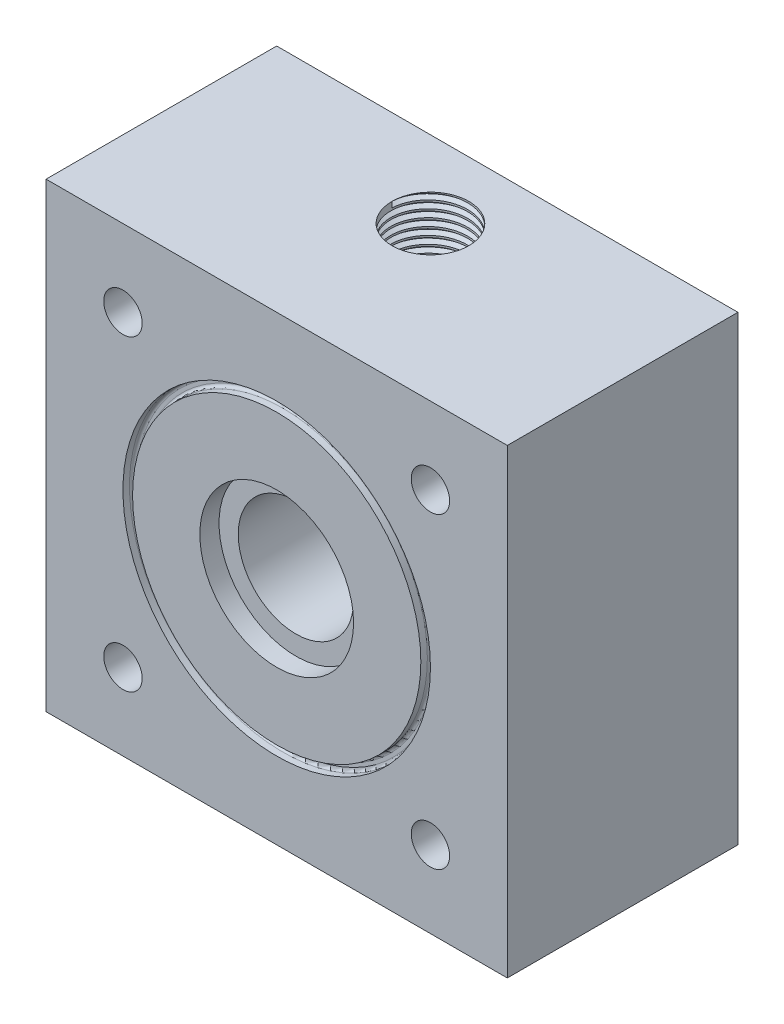
SolidWorks part; units mm, degrees
ref_plane "Front Plane" through (0, 0, 0) normal (0, 0, 1) x (1, 0, 0)
ref_plane "Top Plane" through (0, 0, 0) normal (0, 1, 0) x (1, 0, 0)
ref_plane "Right Plane" through (0, 0, 0) normal (1, 0, 0) x (0, 0, -1)
sketch "Sketch2" plane through (0, 0, 0) normal (0, 0, 1) x (1, 0, 0)
  line L1 (-38.1, -38.1) -> (38.1, -38.1)
  line L2 (-38.1, -38.1) -> (-38.1, 38.1)
  line L3 (-38.1, 38.1) -> (38.1, 38.1)
  line L4 (38.1, -38.1) -> (38.1, 38.1)
  line L5 (-38.1, -38.1) -> (38.1, 38.1) construction
  line L6 (-38.1, 38.1) -> (38.1, -38.1) construction
  point P0 (0, 0)
  dimension "D1" = 76.2
  dimension "D2" = 76.2
extrude "Boss-Extrude1" add sketch "Sketch2" along normal blind 38.1
sketch "Sketch3" plane through (0, 0, 0) normal (0, 0, -1) x (-1, 0, 0)
  circle A0 centre (0, 0) radius 25.4
  circle A1 centre (0, 0) radius 19.05
  dimension "D1" = 50.8
  dimension "D2" = 38.1
extrude "Cut-Extrude1" cut sketch "Sketch3" against normal blind 3.81
sketch "Sketch5" plane through (0, 38.1, 0) normal (0, 1, 0) x (1, 0, 0)
  line L0 (38.1, 0) -> (-38.1, 0) construction
  circle A0 centre (0, -12.7) radius 6.35
  point P4 (0, 0)
  dimension "D1" = 12.7
  dimension "D2" = 12.7
extrude "Cut-Extrude3" cut sketch "Sketch5" against normal blind 38.1
thread "Thread1" pitch 1.27 method cut profile "Thread Profile2" start angle 0, offset 0, length 12.7, pitch 1.27, diameter 12.7
ref_plane "Plane2" through (-6.35, 38.1, 12.7) normal (0, 0, 1) x (-1, 0, 0)
sketch "Thread Profile2" plane through (-6.35, 38.1, 12.7) normal (0, 0, 1) x (-1, 0, 0)
  line L0 (0, 0) -> (0, 1.27) construction
  line L1 (0, 0) -> (0.6874, 0.3969)
  line L2 (0.6874, 0.3969) -> (0.6874, 0.5556)
  line L3 (0.6874, 0.5556) -> (0, 0.9525)
  line L4 (0.6874, 0.4762) -> (0, 0.4762) construction
  line L11 (0, 0) -> (0, 0.9525)
  point P2 (0, 0)
  dimension "Pitch" = 1.27
  dimension "Profile_Angle" = 60
  dimension "Profile_Land" = 0.1588
  dimension "Profile_Height" = 0.6874
sketch "Sketch17" plane through (0, 0, 38.1) normal (0, 0, 1) x (1, 0, 0)
  line L0 (-38.1, 38.1) -> (-38.1, -38.1) construction
  line L1 (38.1, 38.1) -> (-38.1, 38.1) construction
  circle A0 centre (-25.4, 25.4) radius 3.175
  circle A1 centre (25.4, 25.4) radius 3.175
  circle A2 centre (25.4, -25.4) radius 3.175
  circle A3 centre (-25.4, -25.4) radius 3.175
  point P15 (0, 0)
  dimension "D1" = 6.35
  dimension "D2" = 12.7
  dimension "D3" = 12.7
  dimension "D4" = 4
extrude "Cut-Extrude5" cut sketch "Sketch17" against normal through all
sketch "Sketch18" plane through (0, 0, 38.1) normal (0, 0, 1) x (1, 0, 0)
  circle A0 centre (0, 0) radius 12.7
  dimension "D1" = 25.4
extrude "Cut-Extrude6" cut sketch "Sketch18" against normal blind 3.175
sketch "Sketch21" plane through (0, 0, 0) normal (0, 0, -1) x (-1, 0, 0)
  circle A0 centre (0, 0) radius 9.525
  dimension "D1" = 19.05
extrude "Cut-Extrude9" cut sketch "Sketch21" against normal through all
chamfer "Chamfer1" distance 2.54 angle 45 1 edges at (-9.525, 0, 0)
chamfer "Chamfer2" distance 0.508 angle 45 1 edges at (-25.4, 0, 0)
sketch "Sketch22" plane through (0, 0, 38.1) normal (0, 0, 1) x (1, 0, 0)
  circle A0 centre (0, 0) radius 23.8125
  circle A1 centre (0, 0) radius 25.4
  dimension "D1" = 47.625
  dimension "D2" = 50.8
extrude "Cut-Extrude11" cut sketch "Sketch22" against normal blind 1.5875
fillet "Fillet2" radius 0.508 2 edges at (25.4, 0, 36.5125) (23.8125, 0, 36.5125)
chamfer "Chamfer3" distance 0.508 angle 45 1 edges at (-19.05, 0, 0)
fillet "Fillet3" radius 0.762 1 edges at (-25.4, 0, 3.81)
equation "\"D1@Cut-Extrude6\"= 1 / 8"
equation "\"D1@Sketch22\"=1+7/8"
equation "\"D1@Cut-Extrude11\"=1/16"
